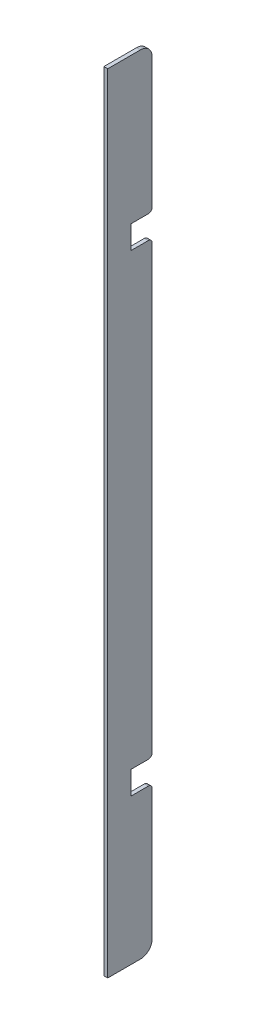
SolidWorks part; units mm, degrees
ref_plane "Front Plane" through (0, 0, 0) normal (0, 0, 1) x (1, 0, 0)
ref_plane "Top Plane" through (0, 0, 0) normal (0, 1, 0) x (1, 0, 0)
ref_plane "Right Plane" through (0, 0, 0) normal (1, 0, 0) x (0, 0, -1)
ref_plane "Plane4" through (-48, 0, 0) normal (-1, 0, 0) x (0, -1, 0)
sketch "Sketch1" plane through (-48, 0, 0) normal (-1, 0, 0) x (0, -1, 0)
  line L0 (-99, -47) -> (99, -47)
  line L1 (102, -44) -> (102, -35.5)
  line L2 (102, -35.5) -> (-102, -35.5)
  line L3 (-102, -35.5) -> (-102, -44)
  arc A0 (-102, -44) -> (-99, -47) centre (-99, -44) ccw
  arc A1 (99, -47) -> (102, -44) centre (99, -44) ccw
extrude "Boss-Extrude1" add sketch "Sketch1" against normal blind 1
sketch "Sketch2" plane through (-47, 0, 0) normal (1, 0, 0) x (0, 0, -1)
  line L0 (41.5, 64.2) -> (47, 64.2) construction
  line L1 (41.5, 58.2) -> (47, 58.2) construction
  line L2 (41.5, 64.2) -> (41.5, 58.2) construction
  line L3 (41.5, 64.2) -> (46, 64.2)
  line L4 (41.5, 58.2) -> (46, 58.2)
  line L5 (41.5, 64.2) -> (41.5, 58.2)
  line L6 (47, 65.2) -> (47, 57.2)
  line L7 (41.5, -64.2) -> (47, -64.2) construction
  line L8 (41.5, -64.2) -> (41.5, -58.2) construction
  line L9 (41.5, -64.2) -> (46, -64.2)
  line L10 (41.5, -64.2) -> (41.5, -58.2)
  line L11 (41.5, -58.2) -> (47, -58.2) construction
  line L12 (41.5, -58.2) -> (46, -58.2)
  line L13 (47, -57.2) -> (47, -65.2)
  arc A0 (46, 64.2) -> (47, 65.2) centre (46, 65.2) ccw construction
  arc A1 (47, 57.2) -> (46, 58.2) centre (46, 57.2) ccw construction
  arc A2 (46, 64.2) -> (47, 65.2) centre (46, 65.2) ccw
  arc A3 (47, 57.2) -> (46, 58.2) centre (46, 57.2) ccw
  arc A4 (47, -65.2) -> (46, -64.2) centre (46, -65.2) ccw construction
  arc A5 (46, -58.2) -> (47, -57.2) centre (46, -57.2) ccw construction
  arc A6 (47, -65.2) -> (46, -64.2) centre (46, -65.2) ccw
  arc A7 (46, -58.2) -> (47, -57.2) centre (46, -57.2) ccw
extrude "Cut-Extrude1" cut sketch "Sketch2" against normal through all
